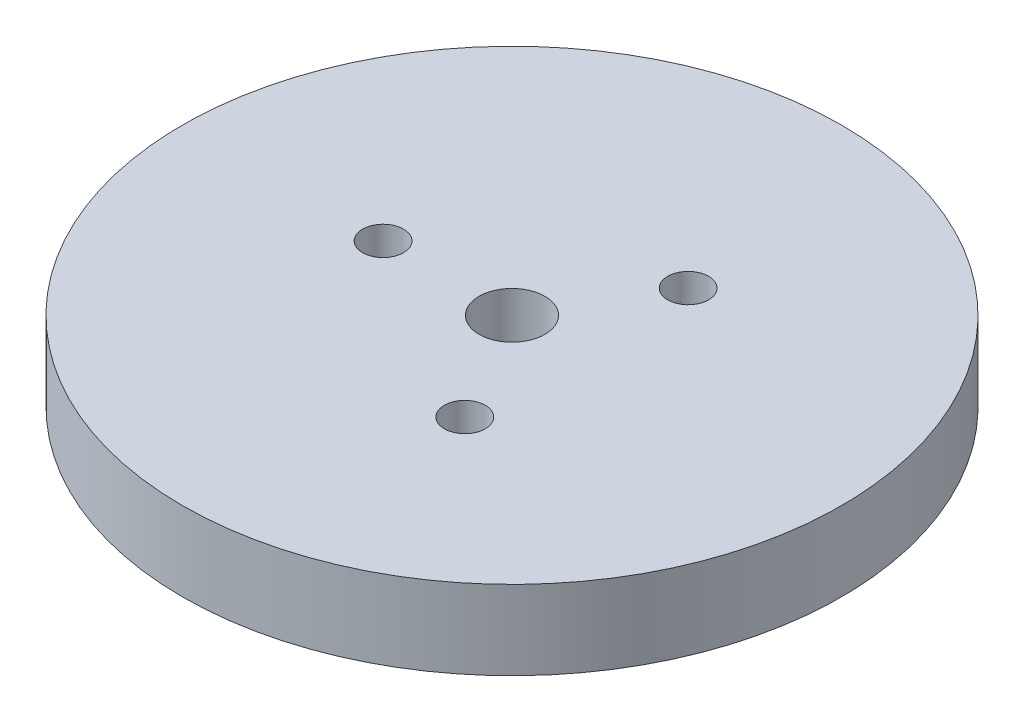
SolidWorks part; units mm, degrees
ref_plane "Front Plane" through (0, 0, 0) normal (0, 0, 1) x (1, 0, 0)
ref_plane "Top Plane" through (0, 0, 0) normal (0, 1, 0) x (1, 0, 0)
ref_plane "Right Plane" through (0, 0, 0) normal (1, 0, 0) x (0, 0, -1)
sketch "Sketch1" plane through (0, 0, 0) normal (0, 1, 0) x (1, 0, 0)
  circle A0 centre (0, 0) radius 75
  dimension "FLANGE_OD" = 150
extrude "Boss-Extrude1" add sketch "Sketch1" along normal blind 18
sketch "Sketch2" plane through (0, 0, 0) normal (0, 1, 0) x (1, 0, 0)
  circle A0 centre (0, 0) radius 7.5
  dimension "BORE_D" = 15
extrude "Cut-Extrude1" cut sketch "Sketch2" along normal through all
sketch "Sketch3" plane through (0, 18, 0) normal (0, 1, 0) x (1, 0, 0)
  circle A0 centre (0, 0) radius 29.3427 construction
  circle A1 centre (-29.3427, 0) radius 4.6515
  dimension "BOLT_D" = 9.3029
  dimension "BOLT_PCD" = 58.6854
extrude "Cut-Extrude2" cut sketch "Sketch3" against normal blind 14.1032
pattern_circular "CirPattern1" count 3 over 360 about axis through (0, 0, 0) along (0, 1, 0) of "Cut-Extrude2"
